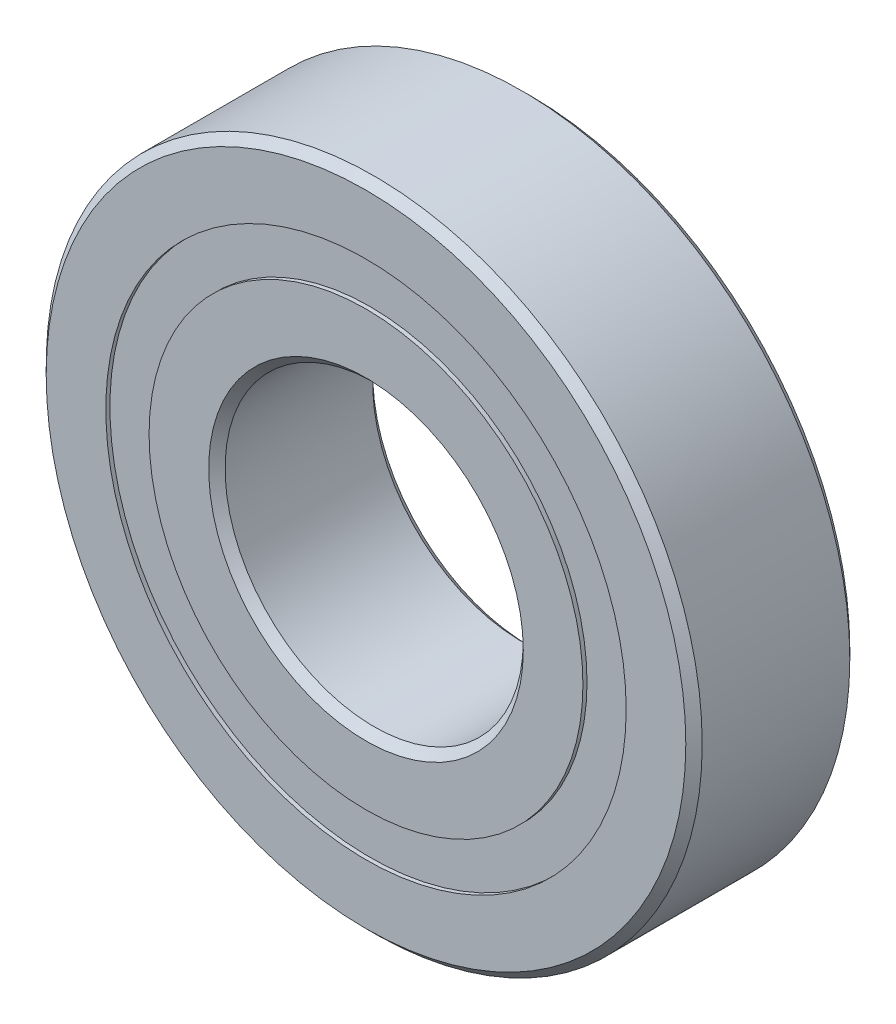
SolidWorks part; units mm, degrees
ref_plane "Front Plane" through (0, 0, 0) normal (0, 0, 1) x (1, 0, 0)
ref_plane "Top Plane" through (0, 0, 0) normal (0, 1, 0) x (1, 0, 0)
ref_plane "Right Plane" through (0, 0, 0) normal (1, 0, 0) x (0, 0, -1)
sketch "Sketch1" plane through (0, 0, 0) normal (1, 0, 0) x (0, 0, -1)
  line L0 (-4.3656, 0) -> (4.3656, 0) construction
  line L1 (0, 17.4625) -> (0, -17.4625) construction
  line L2 (3.9291, 17.4625) -> (-3.9291, 17.4625)
  line L3 (-3.9291, 17.4625) -> (-4.3656, 17.0259)
  line L4 (-4.3656, 17.0259) -> (-4.3656, 13.8514)
  line L5 (-4.3656, 13.8514) -> (-1.9403, 13.8514)
  line L6 (4.3656, 13.8514) -> (1.9403, 13.8514)
  line L7 (4.3656, 17.0259) -> (4.3656, 13.8514)
  line L8 (3.9291, 17.4625) -> (4.3656, 17.0259)
  line L9 (0, 17.4625) -> (0, 12.7) construction
  line L10 (0, 12.7) -> (0, 7.9375) construction
  arc A0 (-1.9403, 13.8514) -> (1.9403, 13.8514) centre (0, 12.7) cw
  point P14 (0, 7.9375)
  dimension "Width" = 8.7312
  dimension "OD" = 34.925
  dimension "D1" = 45
  dimension "D2" = 0.4366
  dimension "Shaft Dia" = 15.875
  dimension "D3" = 3.8806
  dimension "D4" = 1.1514
revolve "Revolve1" add sketch "Sketch1" angle 360 about L0
sketch "Sketch3" plane through (0, 0, 0) normal (1, 0, 0) x (0, 0, -1)
  line L0 (-4.3656, 11.5486) -> (-1.9403, 11.5486)
  line L1 (0, 17.4625) -> (0, -17.4625) construction
  line L2 (-4.3656, 17.0259) -> (-4.3656, 13.8514) construction
  line L3 (-4.3656, 11.5486) -> (-4.3656, 8.3741)
  line L4 (-3.9291, 17.4625) -> (-4.3656, 17.0259) construction
  line L5 (-4.3656, 8.3741) -> (-3.9291, 7.9375)
  line L6 (-3.9291, 7.9375) -> (3.9291, 7.9375)
  line L7 (3.9291, 17.4625) -> (3.9291, -17.4625) construction
  line L8 (3.9291, 7.9375) -> (4.3656, 8.3741)
  line L9 (4.3656, -17.0259) -> (4.3656, 17.0259) construction
  line L10 (4.3656, 8.3741) -> (4.3656, 11.5486)
  line L11 (4.3656, 11.5486) -> (1.9403, 11.5486)
  line L13 (3.9291, 17.4625) -> (4.3656, 17.0259) construction
  arc A0 (1.9403, 13.8514) -> (-1.9403, 13.8514) centre (0, 12.7) ccw construction
  arc A1 (1.9403, 11.5486) -> (-1.9403, 11.5486) centre (0, 12.7) cw
revolve "Revolve3" add sketch "Sketch3" angle 360 about L0
sketch "Sketch4" plane through (0, 0, 0) normal (1, 0, 0) x (0, 0, -1)
  line L0 (-2.2562, 12.7) -> (2.2562, 12.7)
  arc A2 (-2.2562, 12.7) -> (2.2562, 12.7) centre (0, 12.7) cw
  arc A3 (1.9403, 13.8514) -> (-1.9403, 13.8514) centre (0, 12.7) ccw construction
revolve "Revolve4" add sketch "Sketch4" angle 360 about L0
ref_axis "Axis1" through (0, 0, -4.3656) along (0, 0, 1)
pattern_circular "CirPattern1" count 10 every 36 about axis through (0, 0, -4.3656) along (0, 0, 1) of bodies 104
sketch "Sketch5" plane through (0, 0, 0) normal (1, 0, 0) x (0, 0, -1)
  line L0 (-4.3656, 13.8514) -> (-1.9403, 13.8514) construction
  line L1 (-4.1473, 13.8514) -> (-2.2562, 13.8514)
  line L2 (-4.1473, 13.8514) -> (-4.1473, 11.5486)
  line L3 (-4.1473, 11.5486) -> (-2.2562, 11.5486)
  line L4 (-2.2562, 13.8514) -> (-2.2562, 11.5486)
  line L5 (-4.3656, 11.5486) -> (-1.9403, 11.5486) construction
  line L6 (4.3656, 13.8514) -> (1.9403, 13.8514) construction
  line L7 (4.1473, 13.8514) -> (2.2562, 13.8514)
  line L8 (4.1473, 13.8514) -> (4.1473, 11.5486)
  line L9 (4.1473, 11.5486) -> (2.2562, 11.5486)
  line L10 (2.2562, 13.8514) -> (2.2562, 11.5486)
  line L11 (4.3656, 11.5486) -> (1.9403, 11.5486) construction
  line L12 (-3.9291, 17.4625) -> (-4.3656, 17.0259) construction
  point P18 (-4.1473, 17.2442)
revolve "Revolve5" add sketch "Sketch5" angle 360 about L0
equation "\"D2@Sketch1\" = \"Width@Sketch1\"*.05"
equation "\"D3@Sketch1\" = \"Width@Sketch1\"/2.25"
equation "\"D4@Sketch1\" = (((\"OD@Sketch1\"-\"Width@Sketch1\")/2)/3.25)/3.5"
equation "\"D2@CirPattern1\" = 360/\"Balls@CirPattern1\""
